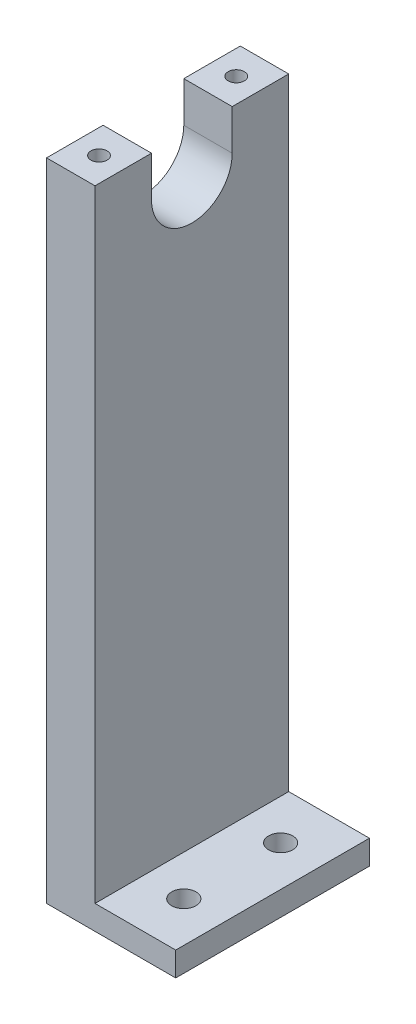
SolidWorks part; units mm, degrees
ref_plane "Front" through (0, 0, 0) normal (0, 0, 1) x (1, 0, 0)
ref_plane "Top" through (0, 0, 0) normal (0, 1, 0) x (1, 0, 0)
ref_plane "Right" through (0, 0, 0) normal (1, 0, 0) x (0, 0, -1)
sketch "Sketch1" plane through (0, 0, 0) normal (0, 1, 0) x (1, 0, 0)
  line L1 (-1.5, -6) -> (1.5, -6)
  line L2 (-1.5, -6) -> (-1.5, 6)
  line L3 (-1.5, 6) -> (1.5, 6)
  line L4 (1.5, -6) -> (1.5, 6)
  line L5 (-1.5, -6) -> (1.5, 6) construction
  line L6 (-1.5, 6) -> (1.5, -6) construction
  point P0 (0, 0)
  point P5 (0, 0)
  dimension "D1" = 3
  dimension "D2" = 12
extrude "Boss-Extrude1" add sketch "Sketch1" along normal blind 40
sketch "Sketch2" plane through (1.5, 0, 0) normal (1, 0, 0) x (0, 0, -1)
  line L0 (-2.5, 40) -> (-2.5, 37.5)
  line L1 (-2.5, 40) -> (2.5, 40)
  line L2 (2.5, 40) -> (2.5, 37.5)
  line L3 (-6, 40) -> (6, 40) construction
  line L4 (0, 1.65) -> (0, -1.65) construction
  arc A0 (2.5, 37.5) -> (-2.5, 37.5) centre (0, 37.5) cw
  dimension "D7" = 2.5
  dimension "D1" = 2.5
  dimension "D2" = 0
  dimension "D3" = 2.5
  dimension "D4" = 0
  dimension "D5" = 2.5
  dimension "D6" = 2.5
extrude "Cut-Extrude1" cut sketch "Sketch2" against normal blind 3
sketch "Sketch3" plane through (0, 40, 0) normal (0, 1, 0) x (1, 0, 0)
  line L2 (-1.5, -6) -> (1.5, -6) construction
  line L3 (1.5, 6) -> (-1.5, 6) construction
  circle A0 centre (0, -4.25) radius 0.5
  circle A1 centre (0, 4.25) radius 0.5
  dimension "D3" = 1
  dimension "D4" = 1
  dimension "D1" = 1.75
  dimension "D2" = 1.75
extrude "Cut-Extrude2" cut sketch "Sketch3" against normal blind 5
sketch "Sketch4" plane through (1.5, 0, 0) normal (1, 0, 0) x (0, 0, -1)
  line L1 (-6, 0) -> (6, 0)
  line L2 (-6, 0) -> (-6, 1.5)
  line L3 (-6, 1.5) -> (6, 1.5)
  line L4 (6, 0) -> (6, 1.5)
  dimension "D1" = 1.5
extrude "Boss-Extrude2" add sketch "Sketch4" along normal blind 5
sketch "Sketch5" plane through (0, 1.5, 0) normal (0, 1, 0) x (1, 0, 0)
  line L1 (6.5, 6) -> (6.5, -6) construction
  line L2 (6.5, 6) -> (1.5, 6) construction
  line L3 (6.5, -6) -> (1.5, -6) construction
  circle A0 centre (4, 3) radius 0.75
  circle A1 centre (4, -3) radius 0.75
  dimension "D5" = 1.5
  dimension "D6" = 1.5
  dimension "D1" = 2.5
  dimension "D2" = 2.5
  dimension "D3" = 3
  dimension "D4" = 3
extrude "Cut-Extrude3" cut sketch "Sketch5" against normal blind 5
